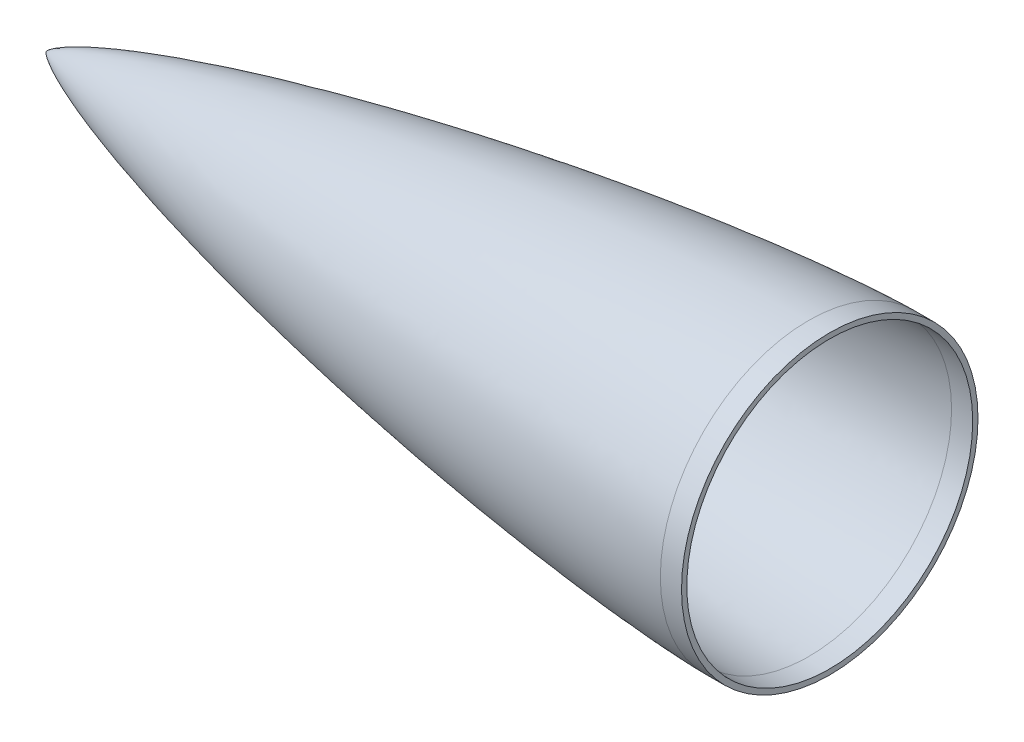
SolidWorks part; units mm, degrees
ref_plane "Front Plane" through (0, 0, 0) normal (0, 0, 1) x (1, 0, 0)
ref_plane "Top Plane" through (0, 0, 0) normal (0, 1, 0) x (1, 0, 0)
ref_plane "Right Plane" through (0, 0, 0) normal (1, 0, 0) x (0, 0, -1)
sketch "Sketch1" plane through (0, 0, 0) normal (0, 0, 1) x (1, 0, 0)
  line L0 (0, 0) -> (457.2, 0) construction
  line L1 (0, 0) -> (0, 88.9) construction
  line L2 (457.2, 88.9151) -> (457.2, 0) construction
  line L3 (457.2, 0) -> (0, 0)
  line L5 (457.2, 0) -> (469.9, 0)
  line L7 (457.2, 88.9151) -> (469.9, 88.9151)
  line L8 (469.9, 0) -> (469.9, 88.9151)
  spline S0 degree 4 poles (0, 0) (0.0023, 0.0117) (0.0082, 0.0346) (0.0259, 0.0787) (0.0695, 0.163) (0.1339, 0.2631) (0.2191, 0.3779) (0.3369, 0.5207) (0.5082, 0.71) (0.7967, 0.9964) (1.2973, 1.4371) (2.1712, 2.1158) (3.7004, 3.1565) (6.4155, 4.7689) (11.1356, 7.1992) (18.8819, 10.6607) (32.1609, 15.8309) (51.2281, 22.2453) (75.2291, 29.3426) (102.987, 36.6637) (131.6184, 43.5191) (160.3731, 49.8355) (189.2264, 55.6835) (218.1627, 61.1047) (247.1713, 66.1244) (276.2447, 70.7536) (305.3776, 74.9923) (334.5665, 78.8281) (363.8087, 82.2339) (389.4414, 84.7941) (411.4449, 86.6328) (428.6333, 87.7894) (439.7384, 88.3858) (448.4262, 88.7338) (453.4393, 88.8671) (455.9463, 88.9096) (457.2, 88.9151) knots 0 0 0 0 0 0.000101 0.000202 0.000405 0.000809 0.001116 0.001422 0.001985 0.002988 0.004584 0.007113 0.011426 0.01877 0.031526 0.052412 0.083828 0.140383 0.203215 0.266046 0.328877 0.391708 0.454539 0.51737 0.580202 0.643033 0.705864 0.768695 0.831526 0.894357 0.925773 0.957189 0.978594 0.989297 1 1 1 1 1 construction
  spline S1 degree 4 poles (0, 0) (0.0023, 0.0117) (0.0082, 0.0346) (0.0259, 0.0787) (0.0695, 0.163) (0.1339, 0.2631) (0.2191, 0.3779) (0.3369, 0.5207) (0.5082, 0.71) (0.7967, 0.9964) (1.2973, 1.4371) (2.1712, 2.1158) (3.7004, 3.1565) (6.4155, 4.7689) (11.1356, 7.1992) (18.8819, 10.6607) (32.1609, 15.8309) (51.2281, 22.2453) (75.2291, 29.3426) (102.987, 36.6637) (131.6184, 43.5191) (160.3731, 49.8355) (189.2264, 55.6835) (218.1627, 61.1047) (247.1713, 66.1244) (276.2447, 70.7536) (305.3776, 74.9923) (334.5665, 78.8281) (363.8087, 82.2339) (389.4414, 84.7941) (411.4449, 86.6328) (428.6333, 87.7894) (439.7384, 88.3858) (448.4262, 88.7338) (453.4393, 88.8671) (455.9463, 88.9096) (457.2, 88.9151) knots 0 0 0 0 0 0.000101 0.000202 0.000405 0.000809 0.001116 0.001422 0.001985 0.002988 0.004584 0.007113 0.011426 0.01877 0.031526 0.052412 0.083828 0.140383 0.203215 0.266046 0.328877 0.391708 0.454539 0.51737 0.580202 0.643033 0.705864 0.768695 0.831526 0.894357 0.925773 0.957189 0.978594 0.989297 1 1 1 1 1
  dimension "D1" = 457.2
  dimension "D2" = 88.9
  dimension "D3" = 12.7
revolve "Revolve1" add sketch "Sketch1" angle 360 about L3
shell "Shell1" thickness 3.175 removed face at (469.9, 0, -88.9151)
